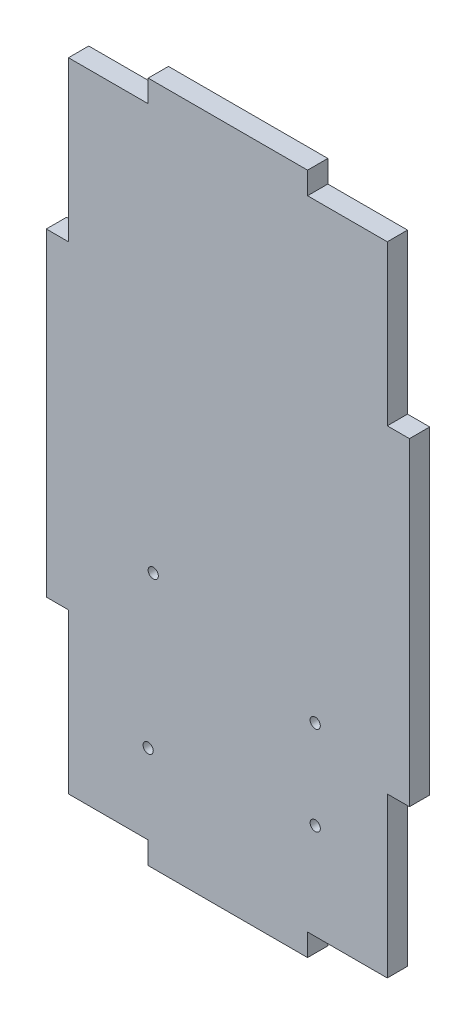
SolidWorks part; units mm, degrees
ref_plane "Front Plane" through (0, 0, 0) normal (0, 0, 1) x (1, 0, 0)
ref_plane "Top Plane" through (0, 0, 0) normal (0, 1, 0) x (1, 0, 0)
ref_plane "Right Plane" through (0, 0, 0) normal (1, 0, 0) x (0, 0, -1)
sketch "Sketch1" plane through (0, 0, 0) normal (0, 0, 1) x (1, 0, 0)
  line L1 (-50, 100) -> (50, 100)
  line L2 (-50, 100) -> (-50, -100)
  line L3 (-50, -100) -> (50, -100)
  line L4 (50, 100) -> (50, -100)
  line L5 (-50, 100) -> (50, -100) construction
  line L6 (-50, -100) -> (50, 100) construction
  point P0 (0, 0)
  dimension "D1" = 200
  dimension "D2" = 100
extrude "Boss-Extrude1" add sketch "Sketch1" along normal blind 6.36
sketch "Sketch2" [suppressed] plane through (0, 0, 3.36) normal (0, 0, 1) x (1, 0, 0)
  line L0 (50, 50) -> (-50, 50) construction
  line L1 (-25, 50) -> (25, 50)
  line L2 (-25, 50) -> (-25, 53.36)
  line L3 (-25, 53.36) -> (25, 53.36)
  line L4 (25, 50) -> (25, 53.36)
  line L5 (0, 0) -> (0, 53.36) construction
  line L6 (0, 0) -> (50, 0) construction
  line L7 (50, -50) -> (50, 50) construction
  dimension "D1" = 6.36
  dimension "D2" = 50
sketch "Sketch8" plane through (0, 0, 0) normal (0, 0, -1) x (-1, 0, 0)
  line L0 (0, 0) -> (0, 100) construction
  line L1 (-50, 100) -> (50, 100) construction
  line L2 (0, 0) -> (50, 0) construction
  line L3 (50, 100) -> (50, -100) construction
  line L5 (-25, 100) -> (25, 100)
  line L6 (-25, 100) -> (-25, 106.96)
  line L7 (-25, 106.96) -> (25, 106.96)
  line L8 (25, 100) -> (25, 106.96)
  dimension "D2" = 6.96
  dimension "D1" = 50
extrude "Boss-Extrude4" add sketch "Sketch8" against normal blind 6.36
mirror "Mirror4" about plane through (0, 0, 0) normal (0, 1, 0) of "Boss-Extrude4"
sketch "Sketch9" plane through (0, 0, 0) normal (0, 0, -1) x (-1, 0, 0)
  line L0 (0, 0) -> (50, 0) construction
  line L1 (50, 100) -> (50, -100) construction
  line L3 (50, 50) -> (56.96, 50)
  line L4 (50, 50) -> (50, -50)
  line L5 (50, -50) -> (56.96, -50)
  line L6 (56.96, 50) -> (56.96, -50)
  dimension "D1" = 100
  dimension "D2" = 6.96
extrude "Boss-Extrude5" add sketch "Sketch9" against normal blind 6.36
mirror "Mirror5" about plane through (0, 0, 0) normal (1, 0, 0) of "Boss-Extrude5"
sketch "Sketch10" plane through (0, 0, 6.36) normal (0, 0, 1) x (1, 0, 0)
  line L0 (0, 0) -> (0, 50) construction
  line L1 (50, 100) -> (25, 100) construction
  line L3 (-22.1665, 100) -> (22.1665, 100)
  line L4 (-22.1665, 100) -> (-22.1665, 90.4825)
  line L5 (-22.1665, 90.4825) -> (22.1665, 90.4825)
  line L6 (22.1665, 100) -> (22.1665, 90.4825)
  dimension "D1" = 9.5175
  dimension "D2" = 44.3329
extrude "Cut-Extrude1" [suppressed] cut sketch "Sketch10" against normal through all and the other way through all
mirror "Mirror6" [suppressed] about plane through (0, 0, 0) normal (0, 1, 0)
sketch "Sketch11" plane through (0, 0, 6.36) normal (0, 0, 1) x (1, 0, 0)
  line L0 (0, 0) -> (50, 0) construction
  line L1 (50, -100) -> (50, -50) construction
  line L3 (50, 18.3322) -> (46.2005, 18.3322)
  line L4 (50, 18.3322) -> (50, -18.3322)
  line L5 (50, -18.3322) -> (46.2005, -18.3322)
  line L6 (46.2005, 18.3322) -> (46.2005, -18.3322)
  dimension "D1" = 3.7995
  dimension "D2" = 36.6643
extrude "Cut-Extrude2" [suppressed] cut sketch "Sketch11" against normal through all and the other way through all
mirror "Mirror7" [suppressed] about plane through (0, 0, 0) normal (1, 0, 0)
sketch "Sketch12" plane through (0, 0, 6.36) normal (0, 0, 1) x (1, 0, 0)
  line L0 (-50, -50) -> (-50, -100) construction
  line L1 (-50, -100) -> (-25, -100) construction
  line L2 (-25, -75) -> (-25, -26.7) construction
  line L3 (27.4, -42) -> (27.4, -69.9) construction
  circle A0 centre (-25, -75) radius 1.6
  circle A1 centre (-23.4, -26.7) radius 1.6
  circle A2 centre (27.4, -69.9) radius 1.6
  circle A3 centre (27.4, -42) radius 1.6
  dimension "D1" = 3.2
  dimension "D2" = 25
  dimension "D3" = 25
  dimension "D5" = 48.3
  dimension "D7" = 5.1
  dimension "D9" = 50.8
  dimension "D10" = 27.9
extrude "arduino holes" cut sketch "Sketch12" against normal through all and the other way through all
sketch "Sketch13" plane through (0, 0, 6.36) normal (0, 0, 1) x (1, 0, 0)
  line L0 (25.9457, -65) -> (-18.2265, -65) construction
  line L1 (50, -100) -> (50, -50) construction
  line L2 (25, -100) -> (50, -100) construction
  circle A0 centre (25.9457, -65) radius 2
  circle A1 centre (-16.3351, -43.7788) radius 2
  circle A2 centre (-16.3351, -86.2212) radius 2
  dimension "D1" = 4
  dimension "D2" = 42.4424
  dimension "D3" = 42.2808
  dimension "D4" = 24.0543
  dimension "D5" = 35
extrude "battery holes" [suppressed] cut sketch "Sketch13" against normal blind 10
sketch "Sketch14" [suppressed] plane through (0, 0, 0) normal (0, 0, -1) x (-1, 0, 0)
  line L6 (33.2, -18.84) -> (45.2, -18.84)
  line L8 (45.2, -29.34) -> (33.2, -29.34)
  line L9 (45.2, -18.84) -> (45.2, -29.34)
  line L10 (33.2, -29.34) -> (33.2, -18.84)
  line L52 (50, -44.24) -> (50, -50)
  line L53 (50, -50) -> (100, -50)
  line L54 (100, -50) -> (100, -25)
  line L55 (100, -25) -> (106.96, -25)
  line L56 (106.96, -25) -> (106.96, 25)
  line L57 (106.96, 25) -> (100, 25)
  line L58 (100, 25) -> (100, 50)
  line L59 (100, 50) -> (50, 50)
  line L60 (50, 50) -> (50, 44.24)
  line L61 (50, 44.24) -> (-50, 44.24)
  line L62 (-50, 44.24) -> (-50, 50)
  line L63 (-50, 50) -> (-100, 50)
  line L64 (-100, 50) -> (-100, 25)
  line L65 (-100, 25) -> (-106.96, 25)
  line L66 (-106.96, 25) -> (-106.96, -25)
  line L67 (-106.96, -25) -> (-100, -25)
  line L68 (-100, -25) -> (-100, -50)
  line L69 (-100, -50) -> (-50, -50)
  line L70 (-50, -50) -> (-50, -44.24)
  line L71 (-50, -44.24) -> (50, -44.24)
  point P0 (-100, 50)
extrude "Cut-Extrude6" [suppressed] cut sketch "Sketch14" against normal through all contours L10 L8 L9 L6
sketch "Sketch15" [suppressed] plane through (0, 0, 0) normal (0, 0, -1) x (-1, 0, 0)
  line L0 (50.6, 25) -> (50.6, -25) construction
  line L1 (27.42, 19.24) -> (30.6, 19.24)
  line L2 (27.42, 19.24) -> (27.42, 6.74)
  line L3 (27.42, 6.74) -> (30.6, 6.74)
  line L4 (30.6, 19.24) -> (30.6, 6.74)
  line L5 (24.7, 44.24) -> (-24.7, 44.24) construction
  dimension "D1" = 12.5
  dimension "D2" = 3.18
  dimension "D3" = 20
  dimension "D4" = 25
extrude "Cut-Extrude7" [suppressed] cut sketch "Sketch15" against normal blind 10
sketch "Sketch16" plane through (0, 0, 0) normal (0, 0, -1) x (-1, 0, 0)
  line L0 (-25, -100) -> (-50, -100) construction
  line L1 (-50, -100) -> (-50, -50) construction
  line L2 (50, -50) -> (50, -100) construction
  circle A0 centre (-10, -80) radius 4
  circle A1 centre (-25, -80) radius 3.35
  circle A2 centre (12, -30) radius 3.35
  dimension "D1" = 8
  dimension "D2" = 6.7
  dimension "D3" = 20
  dimension "D4" = 20
  dimension "D5" = 25
  dimension "D6" = 40
  dimension "D7" = 6.7
  dimension "D8" = 70
  dimension "D9" = 38
extrude "Cut-Extrude8" [suppressed] cut sketch "Sketch16" against normal blind 10
equation "\"Sheet Thickness\"= 6.36mm"
equation "\"Height\"= 100mm"
equation "\"Length\"= 200mm"
equation "\"Width\"= 100mm"
equation "\"D1@Boss-Extrude1\"=\"Sheet Thickness\""
equation "\"D1@Sketch2\"=\"Sheet Thickness\""
equation "\"D2@Sketch2\"=\"Height\"/2"
equation "\"Kerf\"= .60mm"
equation "\"D2@Sketch9\"=\"Sheet Thickness\"+\"Kerf\""
equation "\"D1@Sketch9\"     = \"Length\"/2"
equation "\"D2@Sketch8\"=\"Sheet Thickness\"+\"Kerf\""
equation "\"D1@Sketch10\"=\"Sheet Thickness\"-\"Kerf\""
equation "\"D2@Sketch10\"      = \"Width\"/2"
equation "\"D1@Sketch11\"=\"Sheet Thickness\"-\"Kerf\""
equation "\"D2@Sketch11\"=\"Height\"/2"
